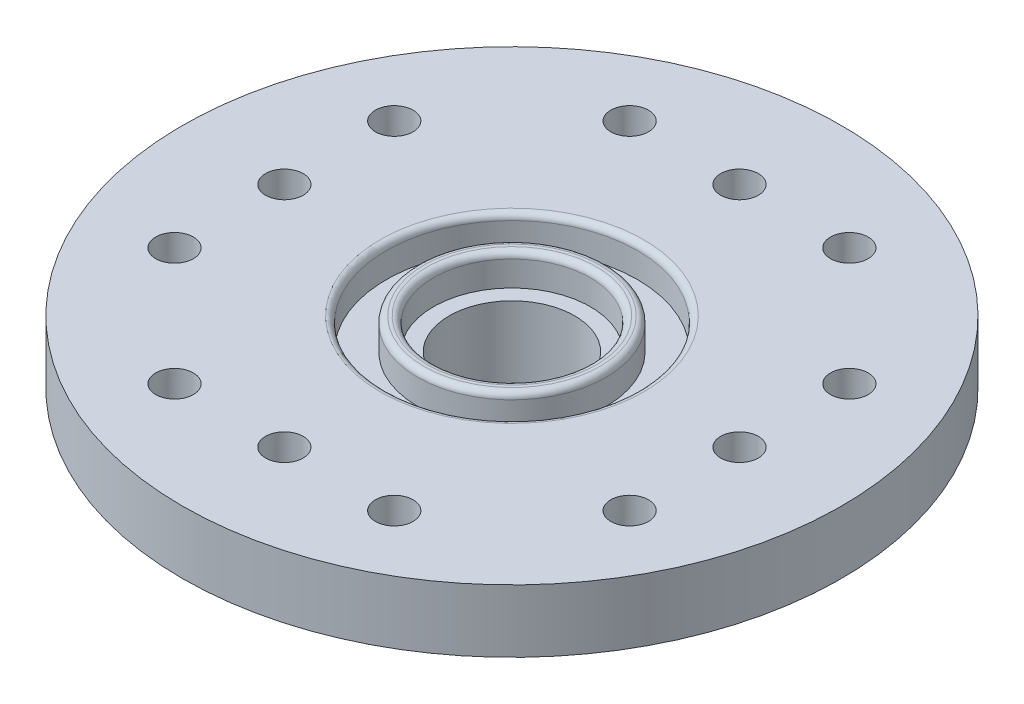
SolidWorks part; units mm, degrees
ref_plane "Alzado" through (0, 0, 0) normal (0, 0, 1) x (1, 0, 0)
ref_plane "Planta" through (0, 0, 0) normal (0, 1, 0) x (1, 0, 0)
ref_plane "Vista lateral" through (0, 0, 0) normal (1, 0, 0) x (0, 0, -1)
sketch "Croquis1" plane through (0, 0, 0) normal (0, 1, 0) x (1, 0, 0)
  circle A0 centre (0, 0) radius 10.5
  dimension "D1" = 21
extrude "Saliente-Extruir1" add sketch "Croquis1" along normal blind 2
sketch "Croquis2" plane through (0, 0, 0) normal (0, -1, 0) x (1, 0, 0)
  circle A0 centre (0, 0) radius 4
  circle A1 centre (0, 0) radius 2
  dimension "D1" = 2
extrude "Saliente-Extruir2" add sketch "Croquis2" along normal blind 3
fillet "Redondeo1" radius 1 1 edges at (0, -3, -4)
sketch "Croquis3" plane through (0, 2, 0) normal (0, 1, 0) x (1, 0, 0)
  circle A3 centre (0, 0) radius 3
  circle A4 centre (0, 0) radius 4
  dimension "D1" = 6
  dimension "D2" = 8
extrude "Cortar-Extruir1" cut sketch "Croquis3" against normal blind 1
sketch "Croquis4" plane through (0, 2, 0) normal (0, 1, 0) x (1, 0, 0)
  circle A2 centre (0, 0) radius 2
  circle A3 centre (0, 0) radius 2
  dimension "D1" = 1
extrude "Cortar-Extruir2" cut sketch "Croquis4" against normal blind 3
sketch "Croquis5" plane through (0, 2, 0) normal (0, 1, 0) x (1, 0, 0)
  circle A4 centre (0, 0) radius 2.5
  circle A5 centre (0, 0) radius 2.5
  dimension "D1" = 0.5
extrude "Cortar-Extruir3" cut sketch "Croquis5" against normal blind 1
sketch "Croquis6" plane through (0, 2, 0) normal (0, 1, 0) x (1, 0, 0)
  line L0 (0, 4) -> (0, 10.5) construction
  line L1 (-5.7527, 7.25) -> (5.838, 7.25) construction
  circle A0 centre (0, 0) radius 7.25 construction
  circle A1 centre (0, 0) radius 4 construction
  circle A2 centre (0, 0) radius 4 construction
  circle A3 centre (0, 0) radius 10.5 construction
  circle A4 centre (0, 7.25) radius 0.6
  circle A5 centre (3.5, 7.25) radius 0.6
  circle A6 centre (-3.5, 7.25) radius 0.6
  dimension "D1" = 14.5
  dimension "D2" = 1.2
  dimension "D3" = 2
  dimension "D4" = 2
extrude "Cortar-Extruir4" cut sketch "Croquis6" against normal through all
pattern_circular "MatrizC1" count 4 over 360 about axis through (0, 2, 0) along (0, 1, 0) of "Cortar-Extruir4"
fillet "Redondeo2" radius 0.2 3 edges at (0, 2, 2.5) (0, 2, 3) (0, 2, 4)
